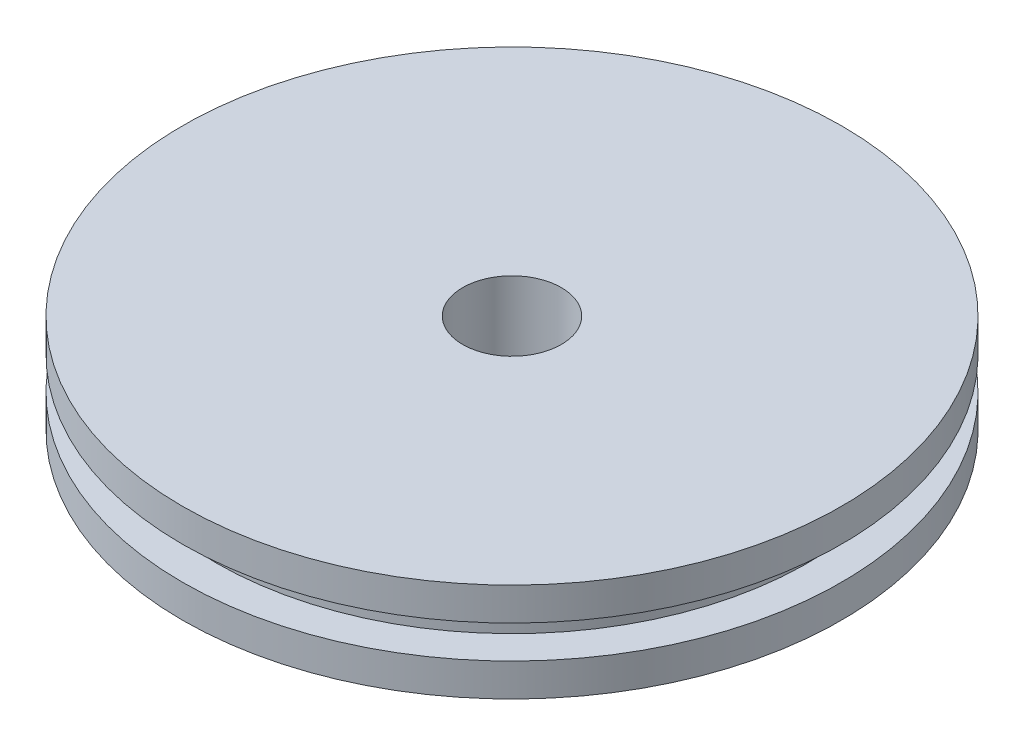
SolidWorks part; units mm, degrees
ref_plane "Front Plane" through (0, 0, 0) normal (0, 0, 1) x (1, 0, 0)
ref_plane "Top Plane" through (0, 0, 0) normal (0, 1, 0) x (1, 0, 0)
ref_plane "Right Plane" through (0, 0, 0) normal (1, 0, 0) x (0, 0, -1)
sketch "Sketch1" plane through (0, 0, 0) normal (0, 1, 0) x (1, 0, 0)
  circle A0 centre (0, 0) radius 21.209
  dimension "D1" = 42.418
extrude "Boss-Extrude1" add sketch "Sketch1" along normal blind 2.1167
sketch "Sketch2" plane through (0, 2.1167, 0) normal (0, 1, 0) x (1, 0, 0)
  circle A0 centre (0, 0) radius 19.05
  dimension "D1" = 38.1
extrude "Boss-Extrude2" add sketch "Sketch2" along normal blind 2.1167
sketch "Sketch3" plane through (0, 4.2333, 0) normal (0, 1, 0) x (1, 0, 0)
  circle A0 centre (0, 0) radius 21.209
  dimension "D1" = 42.418
extrude "Boss-Extrude3" add sketch "Sketch3" along normal blind 2.1167
sketch "Sketch4" plane through (0, 6.35, 0) normal (0, 1, 0) x (1, 0, 0)
  circle A0 centre (0, 0) radius 3.175
  dimension "D1" = 6.35
sketch "Sketch5" plane through (0, 6.35, 0) normal (0, 1, 0) x (1, 0, 0)
  circle A0 centre (0, 0) radius 3.175
  dimension "D1" = 6.35
sketch "Sketch6" plane through (0, 6.35, 0) normal (0, 1, 0) x (1, 0, 0)
  circle A0 centre (0, 0) radius 3.175
  dimension "D1" = 6.35
extrude "Cut-Extrude2" cut sketch "Sketch6" against normal through all
